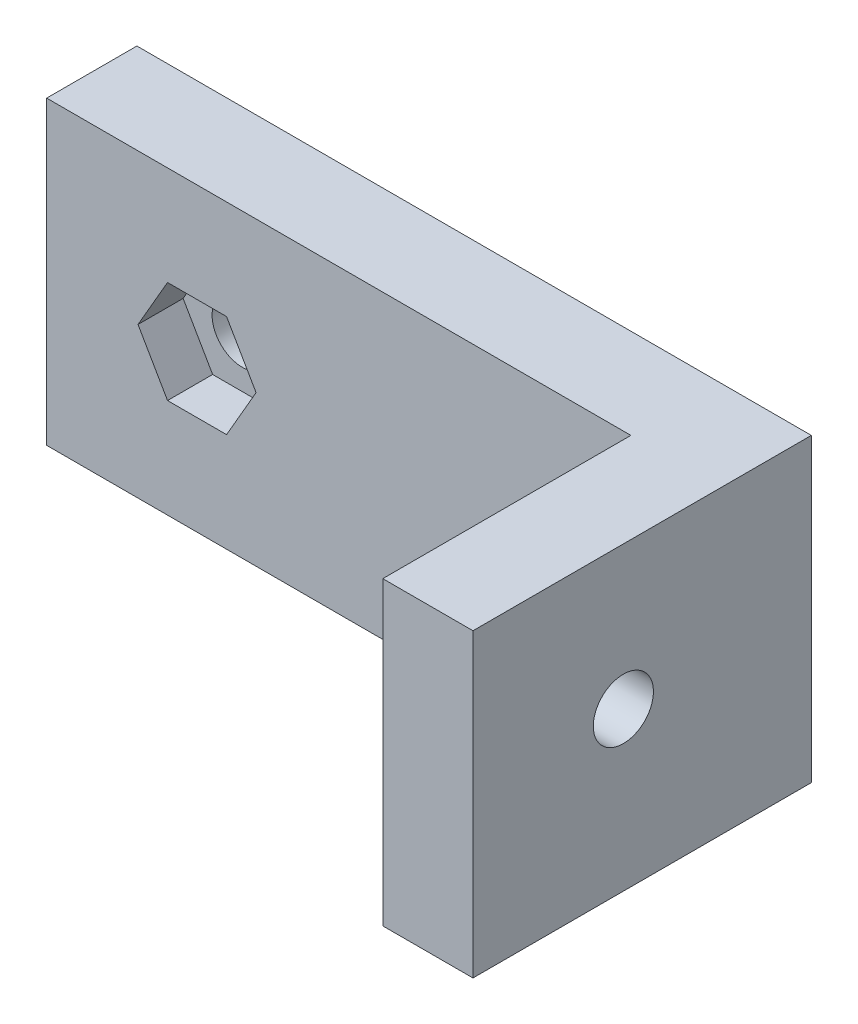
SolidWorks part; units mm, degrees
material "ABS"
ref_plane "Front Plane" through (0, 0, 0) normal (0, 0, 1) x (1, 0, 0)
ref_plane "Top Plane" through (0, 0, 0) normal (0, 1, 0) x (1, 0, 0)
ref_plane "Right Plane" through (0, 0, 0) normal (1, 0, 0) x (0, 0, -1)
sketch "Sketch1" plane through (0, 0, 0) normal (0, 0, 1) x (1, 0, 0)
  line L0 (169.7, 160.9919) -> (169.7, 148.0639) construction
  line L1 (169.7, -7.5) -> (124.85, -7.5)
  line L2 (169.7, -7.5) -> (169.7, 12.5)
  line L3 (169.7, 12.5) -> (124.85, 12.5)
  line L4 (124.85, -7.5) -> (124.85, 12.5)
  line L5 (169.7, -7.5) -> (124.85, 12.5) construction
  line L6 (169.7, 12.5) -> (124.85, -7.5) construction
  line L8 (130.924, 2.5) -> (132.887, -0.9)
  line L9 (132.887, -0.9) -> (136.813, -0.9)
  line L10 (136.813, -0.9) -> (138.776, 2.5)
  line L11 (138.776, 2.5) -> (136.813, 5.9)
  line L12 (136.813, 5.9) -> (132.887, 5.9)
  line L13 (132.887, 5.9) -> (130.924, 2.5)
  circle A0 centre (134.85, 2.5) radius 2
  circle A1 centre (134.85, 2.5) radius 3.4 construction
  point P4 (147.275, 2.5)
  point P10 (134.85, 5.9)
  dimension "D2" = 10
  dimension "D3" = 10
  dimension "D4" = 10
  dimension "D1" = 6.8
extrude "Boss-Extrude1" add sketch "Sketch1" along normal blind 3 contours L4 L1 L2 L3 L13 L12 L11 L10 L9 L8 | L12 L13 L8 L9 L10 L11 A0 region at (147.8556, 2.5, 0) region at (131.9955, 4.1481, 0)
extrude "Boss-Extrude2" add sketch "Sketch1<4>" along normal blind 3 from surface contours L4 L1 L2 L3 L13 L12 L11 L10 L9 L8 region at (147.8556, 2.5, 0) starting at face at (147.275, 2.5, 3)
sketch "Sketch1<4>" plane through (0, 0, 0) normal (0, 0, 1) x (1, 0, 0) same geometry as "Sketch1"
sketch "Sketch5" plane through (169.7, 0, 0) normal (-1, 0, 0) x (0, 0, 1)
  line L0 (6, 12.5) -> (0, 12.5) construction
  line L1 (6, -7.5) -> (22.5, -7.5)
  line L2 (6, -7.5) -> (6, 12.5)
  line L3 (6, 12.5) -> (22.5, 12.5)
  line L4 (22.5, -7.5) -> (22.5, 12.5)
  line L5 (6, -7.5) -> (22.5, 12.5) construction
  line L6 (6, 12.5) -> (22.5, -7.5) construction
  line L8 (12.5, -0.926) -> (15.9, 1.037)
  line L9 (15.9, 1.037) -> (15.9, 4.963)
  line L10 (15.9, 4.963) -> (12.5, 6.926)
  line L11 (12.5, 6.926) -> (9.1, 4.963)
  line L12 (9.1, 4.963) -> (9.1, 1.037)
  line L13 (9.1, 1.037) -> (12.5, -0.926)
  circle A0 centre (12.5, 3) radius 2
  circle A1 centre (12.5, 3) radius 3.4 construction
  point P7 (14.25, 2.5)
  dimension "D1" = 10
  dimension "D2" = 6.8
extrude "Boss-Extrude3" add sketch "Sketch5" along normal blind 3 contours L1 L4 L3 L2 L13 L12 L11 L10 L9 L8 | L12 L13 L8 L9 L10 L11 region at (169.7, 2.5, 6.2593) region at (169.7, 0.1455, 10.8519)
extrude "Boss-Extrude4" add sketch "Sketch5<3>" along normal blind 3 from surface contours L1 L4 L3 L2 L13 L12 L11 L10 L9 L8 region at (169.7, 2.5, 6.2593) starting at face at (166.7, 2.5, 14.25)
sketch "Sketch5<3>" plane through (169.7, 0, 0) normal (-1, 0, 0) x (0, 0, 1) same geometry as "Sketch5"
